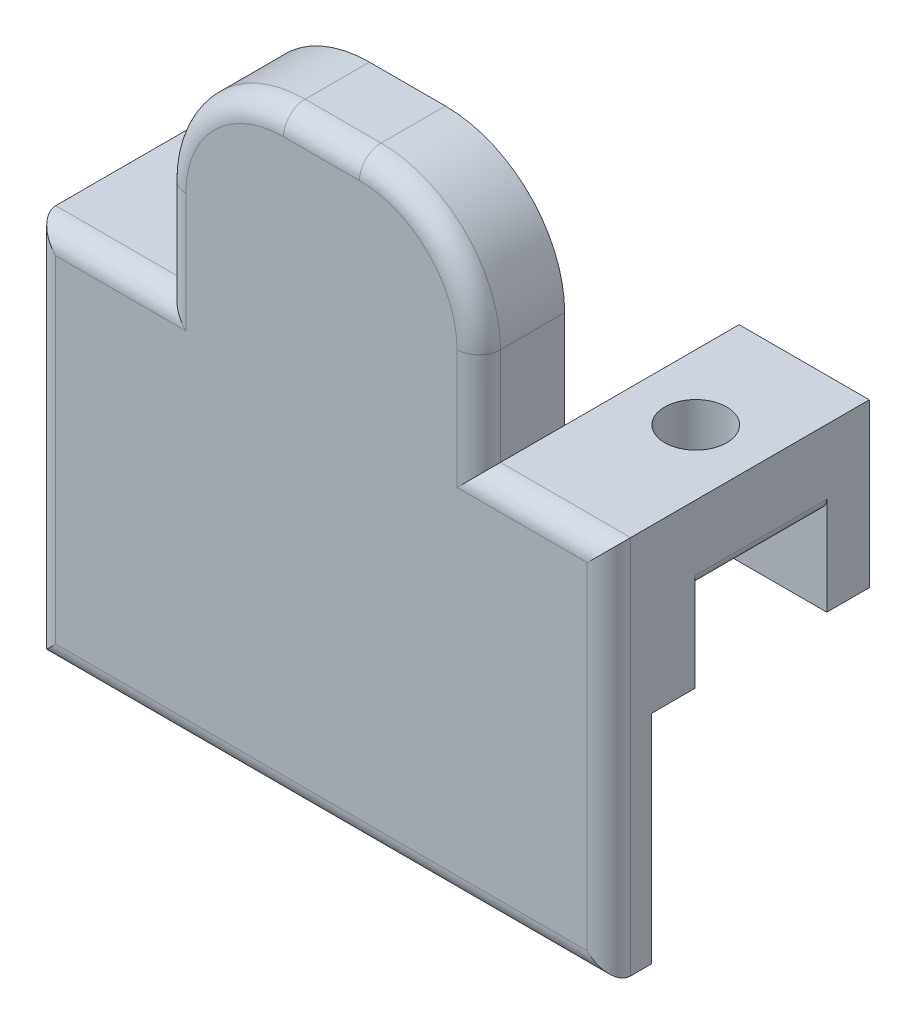
SolidWorks part; units mm, degrees
ref_plane "정면" through (0, 0, 0) normal (0, 0, 1) x (1, 0, 0)
ref_plane "윗면" through (0, 0, 0) normal (0, 1, 0) x (1, 0, 0)
ref_plane "우측면" through (0, 0, 0) normal (1, 0, 0) x (0, 0, -1)
sketch "스케치1" plane through (0, 0, 0) normal (0, 0, 1) x (1, 0, 0)
  line L1 (-26.5, 17.5) -> (26.5, 17.5)
  line L2 (-26.5, 17.5) -> (-26.5, -17.5)
  line L3 (-26.5, -17.5) -> (26.5, -17.5)
  line L4 (26.5, 17.5) -> (26.5, -17.5)
  line L5 (-26.5, 17.5) -> (26.5, -17.5) construction
  line L6 (-26.5, -17.5) -> (26.5, 17.5) construction
  point P0 (0, 0)
  dimension "D1" = 35
  dimension "D2" = 53
extrude "보스-돌출1" add sketch "스케치1" along normal blind 3.92
sketch "스케치2" plane through (0, 0, 3.92) normal (0, 0, 1) x (1, 0, 0)
  line L0 (26.5, 17.5) -> (-26.5, 17.5) construction
  line L1 (-26.5, 17.5) -> (-14.5, 17.5)
  line L2 (-26.5, 17.5) -> (-26.5, -9.5)
  line L3 (-26.5, -9.5) -> (-14.5, -9.5)
  line L4 (-14.5, 17.5) -> (-14.5, -9.5)
  line L5 (14.5, 17.5) -> (26.5, 17.5)
  line L6 (14.5, 17.5) -> (14.5, -9.5)
  line L7 (14.5, -9.5) -> (26.5, -9.5)
  line L8 (26.5, 17.5) -> (26.5, -9.5)
  line L9 (26.5, -17.5) -> (26.5, 17.5) construction
  dimension "D1" = 27
  dimension "D2" = 12
  dimension "D3" = 12
  dimension "D4" = 27
extrude "컷-돌출1" cut sketch "스케치2" against normal blind 4
sketch "스케치3" plane through (0, 0, 0) normal (0, 0, -1) x (-1, 0, 0)
  line L0 (0, 11) -> (0, -11) construction
  line L1 (-14.5, -9.5) -> (-26.5, -9.5)
  line L2 (-14.5, -9.5) -> (-14.5, -2.5)
  line L3 (-14.5, -2.5) -> (-26.5, -2.5)
  line L4 (-26.5, -9.5) -> (-26.5, -2.5)
  line L5 (26.5, -9.5) -> (26.5, -2.5)
  line L6 (14.5, -2.5) -> (26.5, -2.5)
  line L7 (14.5, -9.5) -> (14.5, -2.5)
  line L8 (14.5, -9.5) -> (26.5, -9.5)
  dimension "D1" = 12
  dimension "D2" = 7
extrude "보스-돌출2" add sketch "스케치3" along normal blind 16.08 and the other way through all
sketch "스케치4" plane through (0, -9.5, 0) normal (0, -1, 0) x (1, 0, 0)
  line L0 (-14.5, 0) -> (-14.5, -16.08) construction
  line L1 (-26.5, -16.08) -> (-14.5, -16.08)
  line L2 (-26.5, -16.08) -> (-26.5, -12.16)
  line L3 (-26.5, -12.16) -> (-14.5, -12.16)
  line L4 (-14.5, -16.08) -> (-14.5, -12.16)
  line L5 (26.5, -16.08) -> (14.5, -16.08) construction
  line L6 (14.5, -16.08) -> (26.5, -16.08)
  line L7 (14.5, -16.08) -> (14.5, -12.16)
  line L8 (14.5, -12.16) -> (26.5, -12.16)
  line L9 (26.5, -16.08) -> (26.5, -12.16)
  line L10 (26.5, 0) -> (26.5, -16.08) construction
  dimension "D1" = 3.92
  dimension "D2" = 3.92
extrude "보스-돌출3" add sketch "스케치4" along normal blind 8
sketch "스케치5" plane through (0, -2.5, 0) normal (0, 1, 0) x (1, 0, 0)
  line L0 (-26.5, -3.92) -> (-26.5, 16.08) construction
  line L1 (-26.5, -3.92) -> (-14.5, -3.92) construction
  line L2 (0, -11) -> (0, 11) construction
  circle A0 centre (-20.5, 6.08) radius 2.86
  circle A1 centre (20.5, 6.08) radius 2.86
  dimension "D2" = 5.72
  dimension "D1" = 6
  dimension "D3" = 10
extrude "컷-돌출2" cut sketch "스케치5" against normal through all
sketch "스케치6" plane through (0, 0, 3.92) normal (0, 0, 1) x (1, 0, 0)
  line L0 (14.5, 17.5) -> (-14.5, 17.5) construction
  line L1 (-14.5, -2.5) -> (-14.5, 17.5) construction
  circle A0 centre (0, 2.5) radius 5
  dimension "D3" = 10
  dimension "D1" = 15
  dimension "D2" = 14.5
extrude "컷-돌출3" cut sketch "스케치6" against normal blind 4
sketch "스케치7" plane through (0, 0, 3.92) normal (0, 0, 1) x (1, 0, 0)
  line L0 (-14.5, -2.5) -> (-26.5, -2.5)
  line L1 (-26.5, -2.5) -> (-26.5, -17.5)
  line L2 (-26.5, -17.5) -> (26.5, -17.5)
  line L3 (26.5, -17.5) -> (26.5, -2.5)
  line L4 (26.5, -2.5) -> (14.5, -2.5)
  line L5 (14.5, -2.5) -> (14.5, 17.5)
  line L6 (14.5, 17.5) -> (-14.5, 17.5)
  line L7 (-14.5, 17.5) -> (-14.5, -2.5)
extrude "보스-돌출4" add sketch "스케치7" along normal blind 4
sketch "스케치8" plane through (0, -17.5, 0) normal (0, -1, 0) x (1, 0, 0)
  line L0 (26.5, 7.92) -> (26.5, 0) construction
  line L1 (-26.5, 7.92) -> (26.5, 7.92)
  line L2 (-26.5, 7.92) -> (-26.5, 4)
  line L3 (-26.5, 4) -> (26.5, 4)
  line L4 (26.5, 7.92) -> (26.5, 4)
  dimension "D1" = 3.92
extrude "보스-돌출5" add sketch "스케치8" along normal blind 20
fillet "필렛1" radius 2.5 2 edges at (14.5, -9.5, -6.08) (-14.5, -9.5, -6.08)
fillet "필렛2" radius 11 2 edges at (14.5, 17.5, 3.96) (-14.5, 17.5, 3.96)
fillet "필렛3" radius 1 2 edges at (-26.5, -9.5, -6.08) (26.5, -9.5, -6.08)
fillet "필렛4" radius 2 10 edges at (20.5, -2.5, 7.92) (26.5, -20, 7.92) (0, -37.5, 7.92) (-26.5, -20, 7.92) (-20.5, -2.5, 7.92) (-14.5, 2, 7.92) (-11.2782, 14.2782, 7.92) (0, 17.5, 7.92) (11.2782, 14.2782, 7.92) (14.5, 2, 7.92)
